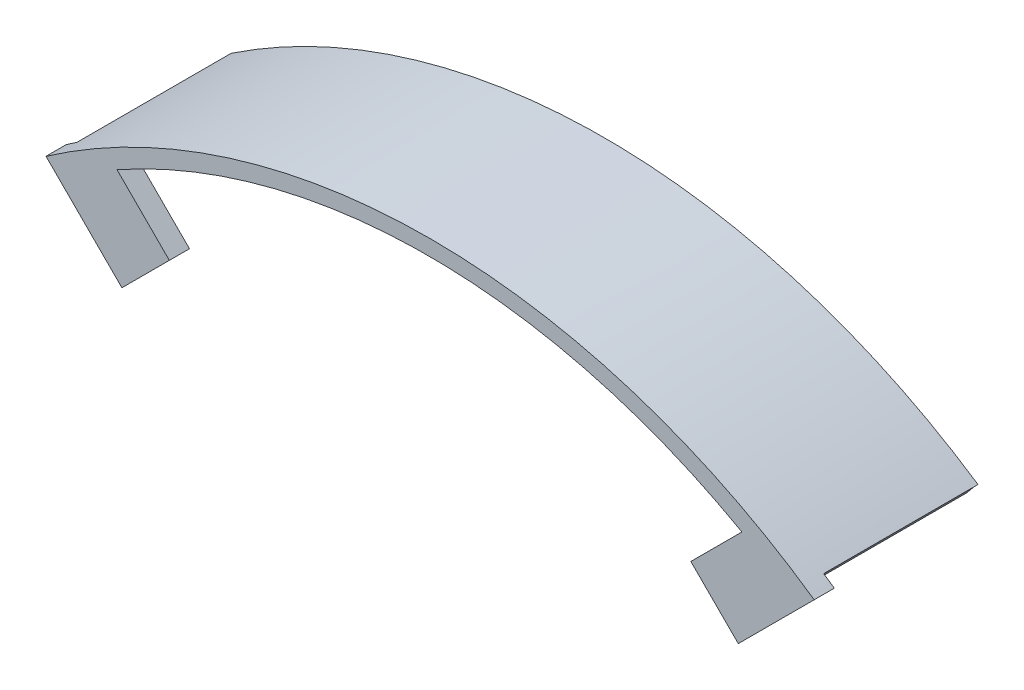
SolidWorks part; units mm, degrees
ref_plane "Alzado" through (0, 0, 0) normal (0, 0, 1) x (1, 0, 0)
ref_plane "Planta" through (0, 0, 0) normal (0, 1, 0) x (1, 0, 0)
ref_plane "Vista lateral" through (0, 0, 0) normal (1, 0, 0) x (0, 0, -1)
sketch "Croquis1" plane through (0, 0, 0) normal (0, 0, 1) x (1, 0, 0)
  circle A0 centre (0, 0) radius 100
  dimension "D1" = 200
extrude "Saliente-Extruir1" add sketch "Croquis1" along normal blind 3
sketch "Croquis3" plane through (0, 0, 3) normal (0, 0, 1) x (1, 0, 0)
  line L0 (0, 0) -> (190, 0) construction
  circle A0 centre (190, 0) radius 110
  dimension "D1" = 220
  dimension "D2" = 190
extrude "Cortar-Extruir1" cut sketch "Croquis3" against normal blind 3
fillet "Redondeo1" radius 10 2 edges at (89.4737, -44.6594, 1.5) (89.4737, 44.6594, 1.5)
sketch "Croquis5" plane through (0, 0, 3) normal (0, 0, 1) x (1, 0, 0)
  line L0 (0, -100) -> (0, 100) construction
  line L1 (-100, 0) -> (80, 0) construction
  line L2 (0, 0) -> (-70.7107, -70.7107) construction
  line L3 (-70.7107, -70.7107) -> (70.7107, 70.7107) construction
  line L4 (0, 0) -> (-70.7107, 70.7107) construction
  line L5 (-70.7107, 70.7107) -> (70.7107, -70.7107) construction
  line L6 (-70.7107, -70.7107) -> (-58.3363, -83.085) construction
  line L9 (-58.3363, -83.085) -> (-83.085, -58.3363)
  line L11 (-83.085, -58.3363) -> (-65.4074, -40.6586)
  line L12 (-65.4074, -40.6586) -> (-40.6586, -65.4074)
  line L13 (-40.6586, -65.4074) -> (-58.3363, -83.085)
  line L14 (-70.7107, 70.7107) -> (-83.085, 58.3363) construction
  line L15 (-83.085, 58.3363) -> (-100, 0) construction
  line L17 (-83.085, 58.3363) -> (-58.3363, 83.085)
  line L18 (-58.3363, 83.085) -> (-40.6586, 65.4074)
  line L19 (-40.6586, 65.4074) -> (-65.4074, 40.6586)
  line L20 (-65.4074, 40.6586) -> (-83.085, 58.3363)
  line L22 (70.7107, -70.7107) -> (58.3363, -83.085) construction
  line L23 (58.3363, -83.085) -> (0, -100) construction
  line L24 (58.3363, -83.085) -> (83.085, -58.3363)
  line L25 (83.085, -58.3363) -> (65.4074, -40.6586)
  line L26 (65.4074, -40.6586) -> (40.6586, -65.4074)
  line L27 (40.6586, -65.4074) -> (58.3363, -83.085)
  line L28 (70.7107, 70.7107) -> (58.3363, 83.085) construction
  line L29 (58.3363, 83.085) -> (0, 100) construction
  line L30 (58.3363, 83.085) -> (83.085, 58.3363)
  line L31 (83.085, 58.3363) -> (65.4074, 40.6586)
  line L32 (65.4074, 40.6586) -> (40.6586, 65.4074)
  line L33 (40.6586, 65.4074) -> (58.3363, 83.085)
  arc A0 (87.1345, 49.0671) -> (87.1345, -49.0671) centre (0, 0) ccw construction
  arc A1 (87.7193, 40.4803) -> (87.7193, -40.4803) centre (190, 0) ccw construction
  point P36 (0, 0)
  dimension "D2" = 17.5
  dimension "D3" = 25
  dimension "D4" = 35
  dimension "D5" = 25
  dimension "D6" = 35
  dimension "D8" = 25
  dimension "D9" = 17.5
  dimension "D7" = 35
  dimension "D10" = 90
  dimension "D11" = 17.5
  dimension "D12" = 17.5
  dimension "D13" = 35
  dimension "D14" = 25
  dimension "D15" = 134.3503
  dimension "D16" = 100
extrude "Cortar-Extruir6" cut sketch "Croquis5" against normal blind 10
sketch "Croquis12" plane through (0, 0, 3) normal (0, 0, 1) x (1, 0, 0)
  line L0 (-53.033, -53.033) -> (-39.9421, -50.0116) construction
  line L1 (-40.6586, -65.4074) -> (-65.4074, -40.6586) construction
  line L2 (-39.9421, -50.0116) -> (-36.8049, -63.6043) construction
  line L3 (-36.8049, -63.6043) -> (-63.6043, -36.8049) construction
  line L4 (-63.6043, -36.8049) -> (-47.6661, -20.8667) construction
  line L6 (53.033, -53.033) -> (-53.033, 53.033) construction
  line L7 (65.4074, -40.6586) -> (40.6586, -65.4074) construction
  line L8 (-65.4074, 40.6586) -> (-40.6586, 65.4074) construction
  line L9 (36.8049, 63.6043) -> (20.8667, 47.6661) construction
  line L10 (63.6043, 36.8049) -> (36.8049, 63.6043) construction
  line L11 (50.0116, 39.9421) -> (63.6043, 36.8049) construction
  line L12 (53.033, 53.033) -> (50.0116, 39.9421) construction
  line L14 (53.033, -53.033) -> (50.2046, -50.2046) construction
  line L15 (50.2046, -50.2046) -> (36.8049, -63.6043) construction
  line L16 (36.8049, -63.6043) -> (63.6043, -36.8049) construction
  line L17 (63.6043, -36.8049) -> (47.6661, -20.8667) construction
  line L19 (-53.033, -53.033) -> (53.033, 53.033) construction
  line L20 (-36.8049, 63.6043) -> (-20.8667, 47.6661) construction
  line L21 (-63.6043, 36.8049) -> (-36.8049, 63.6043) construction
  line L22 (-50.2046, 50.2046) -> (-63.6043, 36.8049) construction
  line L23 (-53.033, 53.033) -> (-50.2046, 50.2046) construction
  circle A0 centre (-63.6043, -36.8049) radius 1.5
  circle A1 centre (-36.8049, -63.6043) radius 1.5
  circle A2 centre (-47.6661, -20.8667) radius 1.5
  circle A3 centre (-20.8667, -47.6661) radius 1.5
  circle A5 centre (47.6661, 20.8667) radius 1.5
  circle A6 centre (20.8667, 47.6661) radius 1.5
  circle A7 centre (63.6043, 36.8049) radius 1.5
  circle A8 centre (36.8049, 63.6043) radius 1.5
  circle A10 centre (20.8667, -47.6661) radius 1.5
  circle A11 centre (47.6661, -20.8667) radius 1.5
  circle A12 centre (63.6043, -36.8049) radius 1.5
  circle A13 centre (36.8049, -63.6043) radius 1.5
  circle A15 centre (-63.6043, 36.8049) radius 1.5
  circle A16 centre (-36.8049, 63.6043) radius 1.5
  circle A17 centre (-20.8667, 47.6661) radius 1.5
  circle A18 centre (-47.6661, 20.8667) radius 1.5
  dimension "D2" = 3
  dimension "D3" = 3
  dimension "D4" = 4
  dimension "D5" = 4
  dimension "D6" = 3
  dimension "D7" = 3
  dimension "D8" = 37.9
  dimension "D9" = 22.54
  dimension "D10" = 22.54
  dimension "D11" = 37.9
  dimension "D12" = 18.95
  dimension "D13" = 18.95
  dimension "D14" = 3
  dimension "D15" = 3
  dimension "D16" = 3
  dimension "D17" = 3
  dimension "D18" = 37.9
  dimension "D19" = 22.54
  dimension "D20" = 22.54
  dimension "D21" = 37.9
  dimension "D22" = 4
  dimension "D1" = 13.95
extrude "Cortar-Extruir7" cut sketch "Croquis12" against normal through all
sketch "Croquis9" plane through (0, 0, 3) normal (0, 0, 1) x (1, 0, 0)
  line L0 (0, 0) -> (-100, 0) construction
  line L5 (0, 100) -> (0, -100) construction
  line L6 (38.9591, 4) -> (43.4591, 4)
  line L7 (38.9591, 4) -> (38.9591, -4)
  line L8 (38.9591, -4) -> (43.4591, -4)
  line L9 (43.4591, 4) -> (43.4591, -4)
  line L10 (-4, -52) -> (4, -52)
  line L11 (-58.1901, 4) -> (-62.6901, 4)
  line L12 (-58.1901, 4) -> (-58.1901, -4)
  line L13 (-58.1901, -4) -> (-62.6901, -4)
  line L14 (-62.6901, 4) -> (-62.6901, -4)
  line L15 (-4, 56.5) -> (4, 56.5)
  line L16 (-4, 56.5) -> (-4, 52)
  line L17 (-4, 52) -> (4, 52)
  line L18 (4, 56.5) -> (4, 52)
  line L19 (4, -56.5) -> (4, -52)
  line L20 (-4, -56.5) -> (4, -56.5)
  line L21 (-4, -56.5) -> (-4, -52)
  line L22 (0, 0) -> (80, 0) construction
  line L24 (-58.2511, -4) -> (-58.2738, -4) construction
  circle A0 centre (71.9, -4) radius 1.5
  circle A1 centre (35.9591, 4) radius 1.5
  circle A4 centre (71.9591, 4) radius 1.5
  circle A5 centre (35.9, -4) radius 1.5
  arc A6 (-81.9939, 57.2451) -> (-81.9939, -57.2451) centre (0, 0) ccw construction
  arc A7 (87.7193, 40.4803) -> (87.7193, -40.4803) centre (190, 0) ccw construction
  circle A8 centre (-91.1901, 4) radius 1.5
  circle A9 centre (-91.1901, -4) radius 1.5
  circle A10 centre (-55.1901, 4) radius 1.5
  circle A11 centre (-55.1901, -4) radius 1.5
  circle A12 centre (-4, 85) radius 1.5
  circle A13 centre (4, 85) radius 1.5
  circle A14 centre (-4, 49) radius 1.5
  circle A15 centre (4, 49) radius 1.5
  circle A20 centre (-4, -49) radius 1.5
  circle A21 centre (4, -49) radius 1.5
  circle A22 centre (4, -85) radius 1.5
  circle A23 centre (-4, -85) radius 1.5
  arc A24 (87.1345, 49.0671) -> (81.9939, 57.2451) centre (0, 0) ccw construction
  arc A25 (57.2451, 81.9939) -> (-57.2451, 81.9939) centre (0, 0) ccw construction
  dimension "D6" = 35.9
  dimension "D7" = 3
  dimension "D8" = 36
  dimension "D9" = 36
  dimension "D10" = 3
  dimension "D11" = 3
  dimension "D12" = 4
  dimension "D13" = 4
  dimension "D14" = 3
  dimension "D15" = 3
  dimension "D16" = 3
  dimension "D21" = 4
  dimension "D22" = 4
  dimension "D23" = 3
  dimension "D24" = 3
  dimension "D25" = 4
  dimension "D26" = 4
  dimension "D27" = 36
  dimension "D28" = 36
  dimension "D29" = 91.1901
  dimension "D30" = 91.1901
  dimension "D35" = 3
  dimension "D36" = 3
  dimension "D37" = 8
  dimension "D38" = 4
  dimension "D39" = 3
  dimension "D40" = 3
  dimension "D41" = 8
  dimension "D42" = 36
  dimension "D43" = 36
  dimension "D44" = 36
  dimension "D45" = 4
  dimension "D46" = 4
  dimension "D51" = 4
  dimension "D52" = 4
  dimension "D53" = 36.1809
  dimension "D55" = 36
  dimension "D56" = 49
  dimension "D57" = 49
  dimension "D58" = 3
  dimension "D59" = 3
  dimension "D60" = 3
  dimension "D61" = 3
  dimension "D62" = 4.5
  dimension "D32" = 8
  dimension "D64" = 0
  dimension "D69" = 8
  dimension "D70" = 4
  dimension "D71" = 85.0941
  dimension "D72" = 85.0941
  dimension "D17" = 4.5
  dimension "D18" = 8
  dimension "D19" = 3
  dimension "D20" = 0
  dimension "D31" = 3.061
  dimension "D33" = 3
  dimension "D34" = 0
  dimension "D47" = 8
  dimension "D48" = 4.5
  dimension "D49" = 0
  dimension "D50" = 3
  dimension "D54" = 4
  dimension "D63" = 0
  dimension "D65" = 3
  dimension "D66" = 4.5
  dimension "D67" = 8
  dimension "D68" = 3
extrude "Cortar-Extruir5" cut sketch "Croquis9" against normal blind 10
sketch "Croquis13" plane through (0, 0, 3) normal (0, 0, 1) x (1, 0, 0)
  line L0 (-57.2451, 81.9939) -> (-53.7096, 78.4583) construction
  line L1 (-40.6586, 65.4074) -> (-57.2451, 81.9939) construction
  line L2 (57.2451, 81.9939) -> (53.4895, 78.2383) construction
  line L3 (57.2451, 81.9939) -> (40.6586, 65.4074) construction
  line L4 (0, 100) -> (0, 95) construction
  line L5 (-53.7096, 78.4583) -> (-40.6586, 65.4074)
  line L6 (-40.6586, 65.4074) -> (-65.4074, 40.6586)
  line L7 (-65.4074, 40.6586) -> (-81.9939, 57.2451)
  line L8 (-81.9939, -57.2451) -> (-65.4074, -40.6586)
  line L9 (-65.4074, -40.6586) -> (-40.6586, -65.4074)
  line L10 (-40.6586, -65.4074) -> (-57.2451, -81.9939)
  line L12 (81.9939, -57.2451) -> (65.4074, -40.6586)
  line L13 (65.4074, -40.6586) -> (40.6586, -65.4074)
  line L14 (40.6586, -65.4074) -> (57.2451, -81.9939)
  line L15 (53.4895, 78.2383) -> (40.6586, 65.4074)
  line L16 (40.6586, 65.4074) -> (65.4074, 40.6586)
  line L17 (65.4074, 40.6586) -> (81.9939, 57.2451)
  arc A0 (57.2451, 81.9939) -> (-57.2451, 81.9939) centre (0, 0) ccw construction
  arc A1 (-53.7096, 78.4583) -> (53.4895, 78.2383) centre (-0.2711, -0.0867) cw
  arc A2 (-81.9939, 57.2451) -> (-81.9939, -57.2451) centre (0, 0) ccw
  arc A3 (-57.2451, -81.9939) -> (57.2451, -81.9939) centre (0, 0) ccw
  arc A4 (87.7193, -40.4803) -> (87.7193, 40.4803) centre (190, 0) cw
  arc A7 (81.9939, -57.2451) -> (87.7193, -40.4803) centre (81.3824, -47.6762) ccw
  arc A8 (81.9939, 57.2451) -> (87.7193, 40.4803) centre (84.8566, 48.8627) cw
  dimension "D2" = 95
  dimension "D3" = 100
  dimension "D4" = 110
  dimension "D5" = 100
  dimension "D6" = 0.2846
  dimension "D7" = 17.753
  dimension "D1" = 5
extrude "Cortar-Extruir9" cut sketch "Croquis13" against normal through all
sketch "Croquis14" plane through (0, 0, 0) normal (0, 0, -1) x (-1, 0, 0)
  line L1 (45.9314, 70.6802) -> (38.8604, 77.7512)
  line L4 (-45.9314, 70.6802) -> (-38.8604, 77.7512)
  line L6 (45.9314, 70.6802) -> (53.7096, 78.4583)
  line L7 (38.8604, 77.7512) -> (44.8915, 83.7824)
  line L8 (-45.9314, 70.6802) -> (-53.4895, 78.2383)
  line L9 (-38.8604, 77.7512) -> (-44.7026, 83.5935)
  arc A3 (53.7096, 78.4583) -> (-53.4895, 78.2383) centre (0.2711, -0.0867) ccw construction
  arc A4 (53.7096, 78.4583) -> (44.8915, 83.7824) centre (0.2711, -0.0867) ccw
  arc A5 (-53.4895, 78.2383) -> (-44.7026, 83.5935) centre (0.2711, -0.0867) cw
  dimension "D4" = 95
  dimension "D8" = 95
  dimension "D1" = 10.6888
  dimension "D2" = 10
  dimension "D3" = 8.2622
  dimension "D5" = 8.5293
  dimension "D6" = 10
  dimension "D7" = 11
  dimension "D9" = 82.7098
extrude "Saliente-Extruir3" add sketch "Croquis14" against normal blind 3
sketch "Croquis15" plane through (0, 0, 3) normal (0, 0, 1) x (1, 0, 0)
  line L0 (57.2451, 81.9939) -> (45.9314, 70.6802)
  line L1 (45.9314, 70.6802) -> (38.8604, 77.7512)
  line L2 (38.8604, 77.7512) -> (44.7026, 83.5935)
  line L3 (-44.8915, 83.7824) -> (-38.8604, 77.7512)
  line L4 (-38.8604, 77.7512) -> (-45.9314, 70.6802)
  line L5 (-45.9314, 70.6802) -> (-57.2451, 81.9939)
  line L8 (0, 100) -> (0, 97.5) construction
  arc A0 (57.2451, 81.9939) -> (-57.2451, 81.9939) centre (0, 0) ccw
  arc A1 (44.7026, 83.5935) -> (-44.8915, 83.7824) centre (-0.2711, -0.0867) ccw
  dimension "D1" = 100
  dimension "D2" = 95
  dimension "D3" = 2.5
extrude "Saliente-Extruir4" add sketch "Croquis15" along normal blind 23
sketch "Croquis16" plane through (0, 0, 0) normal (0, 0, -1) x (-1, 0, 0)
  line L0 (-44.7026, 83.5935) -> (-46.4704, 85.3612)
  line L1 (44.8915, 83.7824) -> (46.6592, 85.5501)
  arc A0 (-46.4704, 85.3612) -> (46.6592, 85.5501) centre (0.2624, 2.6506) cw
  arc A1 (-44.7026, 83.5935) -> (44.8915, 83.7824) centre (0.2711, -0.0867) cw
  arc A2 (57.2451, 81.9939) -> (-57.2451, 81.9939) centre (0, 0) ccw construction
  dimension "D3" = 95
  dimension "D4" = 95
  dimension "D5" = 2.6635
  dimension "D1" = 2.5
  dimension "D2" = 2.5
extrude "Cortar-Extruir10" cut sketch "Croquis16" against normal through all
sketch "Croquis17" plane through (0, 0, 0) normal (0, 0, -1) x (-1, 0, 0)
  line L0 (-45.9314, 70.6802) -> (-55.4774, 80.2261)
  line L1 (-57.2451, 81.9939) -> (-45.9314, 70.6802) construction
  line L2 (-45.9314, 70.6802) -> (-38.8604, 77.7512)
  line L3 (-38.8604, 77.7512) -> (-46.4704, 85.3612)
  line L4 (46.6592, 85.5501) -> (38.8604, 77.7512)
  line L5 (38.8604, 77.7512) -> (45.9314, 70.6802)
  line L6 (57.2451, 81.9939) -> (55.4774, 80.2261) construction
  line L7 (45.9314, 70.6802) -> (57.2451, 81.9939) construction
  line L8 (55.4774, 80.2261) -> (45.9314, 70.6802)
  line L9 (-46.4704, 85.3612) -> (-55.4774, 80.2261)
  line L10 (55.4774, 80.2261) -> (46.6592, 85.5501)
  dimension "D1" = 13.5
  dimension "D2" = 13.5
extrude "Cortar-Extruir11" cut sketch "Croquis17" against normal blind 23
sketch "Croquis20" plane through (0, 0, 0) normal (0, 0, -1) x (-1, 0, 0)
  line L0 (57.2451, 81.9939) -> (55.4774, 80.2261)
  line L1 (55.4774, 80.2261) -> (46.6592, 85.5501) construction
  line L2 (55.5571, 83.0598) -> (53.7616, 81.262)
  line L3 (-57.2451, 81.9939) -> (-55.4774, 80.2261)
  line L4 (-46.4704, 85.3612) -> (-55.4774, 80.2261) construction
  line L5 (-53.927, 81.11) -> (-55.5535, 83.0598)
  arc A0 (55.4774, 80.2261) -> (53.7616, 81.262) centre (55.1321, 81.5932) cw
  arc A1 (57.2451, 81.9939) -> (55.5571, 83.0598) centre (55.8682, 81.6828) ccw
  arc A2 (57.2451, 81.9939) -> (-57.2451, 81.9939) centre (0, 0) ccw construction
  arc A3 (-55.4774, 80.2261) -> (-53.927, 81.11) centre (-55.1441, 81.4432) ccw
  arc A4 (-57.2451, 81.9939) -> (-55.5535, 83.0598) centre (-55.8663, 81.681) cw
  dimension "D1" = 1.4117
  dimension "D2" = 1.41
  dimension "D4" = 0.736
  dimension "D5" = 98.9613
  dimension "D7" = 0.8923
  dimension "D8" = 98.9588
  dimension "D9" = 0.7222
  dimension "D10" = 1.2619
  dimension "D3" = 2.5409
  dimension "D6" = 2.5391
extrude "Cortar-Extruir14" cut sketch "Croquis20" against normal blind 23
